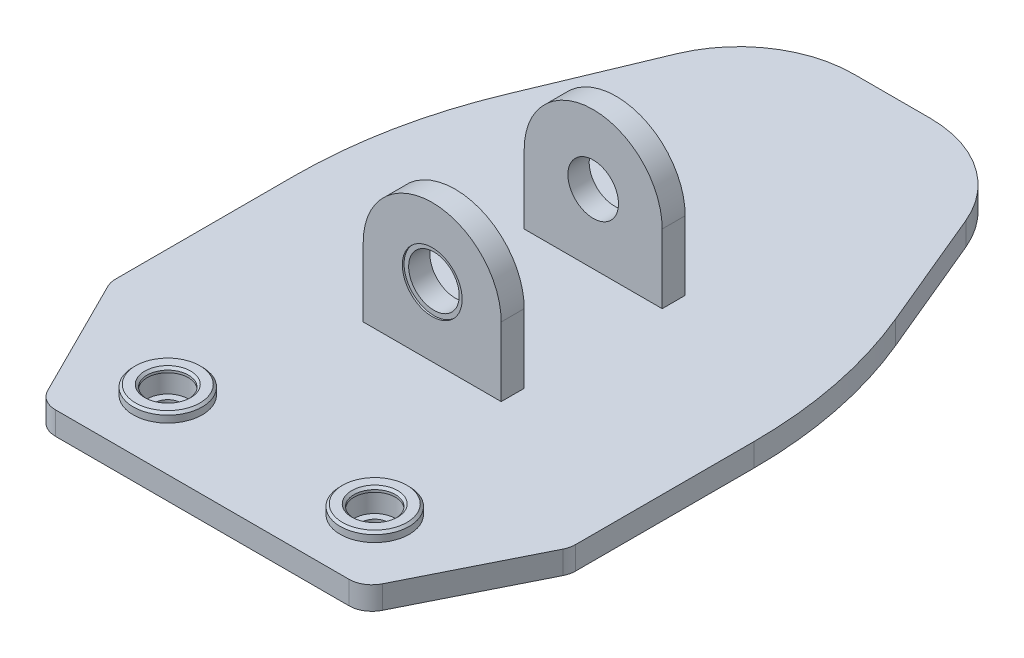
SolidWorks part; units mm, degrees
ref_plane "前视基准面" through (0, 0, 0) normal (0, 0, 1) x (1, 0, 0)
ref_plane "上视基准面" through (0, 0, 0) normal (0, 1, 0) x (1, 0, 0)
ref_plane "右视基准面" through (0, 0, 0) normal (1, 0, 0) x (0, 0, -1)
other "Configuration Table"
sketch "草图1" plane through (0, 0, 0) normal (0, 1, 0) x (1, 0, 0)
  line L0 (0, 0) -> (0, 255.8207) construction
  line L1 (-100, 0) -> (100, 0)
  line L2 (100, 0) -> (100, 180)
  line L3 (100, 180) -> (50, 300)
  line L4 (50, 300) -> (-50, 300)
  line L5 (-100, 180) -> (-50, 300)
  line L6 (-100, 0) -> (-100, 180)
  point P8 (0, 300)
  dimension "D1" = 300
  dimension "D2" = 100
  dimension "D3" = 120
  dimension "D4" = 50
extrude "凸台-拉伸1" add sketch "草图1" along normal blind 10
sketch "草图2" plane through (100, 0, 0) normal (1, 0, 0) x (0, 0, -1)
  line L0 (40, 100) -> (40, -10.3339) construction
  line L1 (0, 10) -> (0, 0) construction
  line L2 (0, 10) -> (0, 60)
  line L3 (80, 10) -> (80, 60)
  arc A0 (80, 60) -> (0, 60) centre (40, 60) ccw
  circle A1 centre (40, 60) radius 10
  line M6 (180, 10) -> (0, 10)
  dimension "D3" = 20
  dimension "D1" = 40
  dimension "D2" = 50
extrude "凸台-拉伸2" [suppressed] add sketch "草图2" against normal up to surface (200 mm away) contours A0 L0 A1 L3 M6 | L0 A0 L2 A1 M6 up to face at (-100, 5, -90)
sketch "草图3" [suppressed] plane through (0, 10, 0) normal (0, 1, 0) x (1, 0, 0)
  line L0 (0, 0) -> (0, 135.8056) construction
  line L1 (-100, 0) -> (100, 0) construction
  line L2 (-70, 0) -> (70, 0)
  line L3 (-70, 0) -> (-70, 100)
  line L4 (-70, 100) -> (70, 100)
  line L5 (70, 0) -> (70, 100)
  line L6 (100, 0) -> (100, 80) construction
  line L7 (-100, 80) -> (-100, 0) construction
  dimension "D1" = 30
  dimension "D2" = 30
  dimension "D3" = 100
extrude "切除-拉伸1" [suppressed] cut sketch "草图3" along normal blind 171
sketch "草图4" plane through (0, 0, 0) normal (0, 0, 1) x (1, 0, 0)
  line L0 (0, 0) -> (0, 92.3322) construction
  line L1 (30, 40) -> (30, 10)
  line L2 (-30, 40) -> (-30, 10)
  line L3 (-100, 10) -> (100, 10) construction
  arc A0 (-30, 40) -> (30, 40) centre (0, 40) cw
  circle A1 centre (0, 40) radius 11
  line M10 (100, 10) -> (-100, 10)
  dimension "D2" = 30
  dimension "D3" = 22
  dimension "D1" = 30
extrude "凸台-拉伸3" add sketch "草图4" against normal blind 80 from offset 100 contours L0 L1 A0 A1 M10 | L0 A1 A0 L2 M10 region at (-15.2547, 36.8238, 0) region at (15.2547, 36.8238, 0) offset against normal yes
sketch "草图5" plane through (0, 10, 0) normal (0, 1, 0) x (1, 0, 0)
  line L0 (-47.074, 140) -> (51.1394, 140) construction
  line L1 (30, 180) -> (-30, 180) construction
  line L2 (30, 100) -> (-30, 100) construction
  line L3 (-30, 100) -> (30, 100) construction
  line L4 (-40, 170) -> (40, 170)
  line L5 (-40, 170) -> (-40, 110)
  line L6 (-40, 110) -> (40, 110)
  line L7 (40, 170) -> (40, 110)
  line L8 (30, 180) -> (30, 100) construction
  line L9 (-30, 180) -> (-30, 100) construction
  dimension "D1" = 10
  dimension "D2" = 10
  dimension "D3" = 10
  dimension "D4" = 10
extrude "切除-拉伸2" cut sketch "草图5" along normal blind 110 contours L7 L6 L5 L4
fillet "圆角1" radius 50 2 edges at (-50, 5, -300) (50, 5, -300)
fillet "圆角2" radius 200 2 edges at (-100, 5, -180) (100, 5, -180)
sketch "草图6" [suppressed] plane through (100, 0, 0) normal (1, 0, 0) x (0, 0, -1)
  line L0 (40, 60) -> (40, -52.2503) construction
  circle A0 centre (40, 60) radius 10 construction
  circle A1 centre (40, 60) radius 10 construction
  arc A2 (73.0468, 82.5368) -> (6.9532, 82.5368) centre (40, -25) ccw
  arc A3 (80, 60) -> (0, 60) centre (40, 60) ccw construction
  arc A4 (73.0468, 82.5368) -> (6.9532, 82.5368) centre (40, 60) ccw
  dimension "D2" = 225
  dimension "D1" = 25
extrude "切除-拉伸3" [suppressed] cut sketch "草图6" against normal through all both and the other way through all contours A2 A4
sketch "草图7" plane through (0, 10, 0) normal (0, 1, 0) x (1, 0, 0)
  line L0 (0, 0) -> (0, 141.3983) construction
  line L1 (-100, 0) -> (100, 0) construction
  circle A0 centre (45, 30) radius 9
  dimension "D1" = 18
  dimension "D2" = 45
  dimension "D3" = 30
extrude "切除-拉伸6" cut sketch "草图7" against normal offset from surface (6 mm away) 4 contours A0 up to face at (0, 0, -186.7805)
sketch "草图10" plane through (0, 4, 0) normal (0, 1, 0) x (1, 0, 0)
  circle A0 centre (45, 30) radius 6
  dimension "D1" = 12
extrude "切除-拉伸7" cut sketch "草图10" against normal blind 28 contours A0
sketch "草图11" plane through (0, 10, 0) normal (0, 1, 0) x (1, 0, 0)
  circle A0 centre (45, 30) radius 12.5
  circle A1 centre (45, 30) radius 16.5
  dimension "D1" = 25
  dimension "D2" = 33
extrude "切除-拉伸8" [suppressed] cut sketch "草图11" against normal blind 5
sketch "草图12" plane through (0, 10, 0) normal (0, 1, 0) x (1, 0, 0)
  circle A0 centre (45, 30) radius 15
  dimension "D1" = 30
extrude "凸台-拉伸5" add sketch "草图12" along normal blind 4 contours A0
sketch "草图13" plane through (0, 14, 0) normal (0, 1, 0) x (1, 0, 0)
  circle A0 centre (45, 30) radius 9
  dimension "D1" = 18
extrude "切除-拉伸9" cut sketch "草图13" against normal blind 4
sketch "草图14" plane through (0, 14, 0) normal (0, 1, 0) x (1, 0, 0)
  circle A0 centre (45, 30) radius 9.75
  circle A2 centre (45, 30) radius 9 construction
  circle A3 centre (45, 30) radius 9
  circle M1 centre (45, 30) radius 9
  dimension "D1" = 19.5
extrude "卡簧槽" cut sketch "草图14" against normal blind 10 from offset 2 contours M1 | A0 region at (45, 14, -30) offset against normal yes
chamfer "倒角1" distance 1 angle 45 2 edges at (45, 14, -15) (45, 14, -21)
ref_plane "基准面1" through (0, 0, 0) normal (-1, 0, 0) x (0, 0, 1)
mirror "镜向1" about plane through (0, 0, 0) normal (-1, 0, 0) of "切除-拉伸6", "切除-拉伸7", "凸台-拉伸5", "切除-拉伸9", "卡簧槽", "倒角1"
sketch "草图16" plane through (0, 0, -100) normal (0, 0, 1) x (1, 0, 0)
  circle A0 centre (0, 40) radius 13
  dimension "D1" = 26
extrude "切除-拉伸10" cut sketch "草图16" against normal blind 0.75
sketch "草图17" plane through (0, 0, -180) normal (0, 0, -1) x (-1, 0, 0)
  circle A0 centre (0, 40) radius 13
  dimension "D1" = 26
extrude "切除-拉伸11" cut sketch "草图17" against normal blind 0.75 contours A0
sketch "草图18" plane through (-100, 0, 0) normal (-1, 0, 0) x (0, 0, 1)
  line L0 (-30, 92.2697) -> (-30, -20.0308) construction
  line L1 (-40, 10) -> (-40, 30)
  line L2 (-140, 10) -> (0, 10) construction
  line L3 (-20, 30) -> (-20, 10)
  line L4 (-40, 10) -> (-20, 10)
  arc A0 (-20, 30) -> (-40, 30) centre (-30, 30) ccw
  circle A1 centre (-30, 30) radius 2.5
  dimension "D2" = 5
  dimension "D4" = 10
  dimension "D1" = 30
  dimension "D3" = 20
extrude "凸台-拉伸6" [suppressed] add sketch "草图18" against normal up to surface (200 mm away) contours A1 L0 | L0 A1 | L3 L4 L1 A0 up to face at (100, 5, -70)
sketch "草图20" plane through (0, 10, 0) normal (0, 1, 0) x (1, 0, 0)
  line L0 (0, 0) -> (0, 309.5578) construction
  line L1 (-100, 0) -> (100, 0) construction
  line L2 (-60.0864, 49.2403) -> (-60.0864, 11.6041)
  line L3 (75.0864, 51.8093) -> (107.8414, 51.8093)
  line L4 (75.0864, 51.8093) -> (75.0864, 7.1083)
  line L5 (75.0864, 7.1083) -> (107.8414, 7.1083)
  line L6 (107.8414, 51.8093) -> (107.8414, 7.1083)
  line L7 (15, 49.2403) -> (60.0864, 49.2403)
  line L8 (15, 49.2403) -> (15, 11.6041)
  line L9 (15, 11.6041) -> (60.0864, 11.6041)
  line L10 (60.0864, 49.2403) -> (60.0864, 11.6041)
  line L11 (-15, 11.6041) -> (-60.0864, 11.6041)
  line L12 (-15, 49.2403) -> (-15, 11.6041)
  line L13 (-15, 49.2403) -> (-60.0864, 49.2403)
  line L14 (-107.8414, 51.8093) -> (-107.8414, 7.1083)
  line L15 (-75.0864, 7.1083) -> (-107.8414, 7.1083)
  line L16 (-75.0864, 51.8093) -> (-75.0864, 7.1083)
  line L17 (-75.0864, 51.8093) -> (-107.8414, 51.8093)
  dimension "D1" = 15
  dimension "D2" = 15
extrude "切除-拉伸12" [suppressed] cut sketch "草图20" along normal through all
chamfer "倒角2" distance 30 distance2 60 1 edges at (100, 5, 0) first distance on face at (0, 5, 0)
chamfer "倒角3" distance 60 distance2 30 1 edges at (-100, 5, 0) first distance on face at (-100, 5, -70)
fillet "圆角3" radius 10 4 edges at (-70, 5, 0) (-100, 5, -60) (70, 5, 0) (100, 5, -60)
ref_plane "脚底板中心面" through (0, 0, 0) normal (-1, 0, 0) x (0, 0, 1)
ref_plane "基准面3" through (0, 0, -30) normal (0, 0, 1) x (1, 0, 0)
sketch "草图22" plane through (0, 0, -30) normal (0, 0, 1) x (1, 0, 0)
  line L0 (45, 18.5577) -> (45, -23.1228) construction
  line L1 (-45, 24.8334) -> (-45, -23.1228) construction
  line L2 (45, 0) -> (45, 4) construction
  line L3 (-45, 0) -> (-45, 4) construction
ref_plane "基准面4" through (-45, 0, 0) normal (-1, 0, 0) x (0, 0, 1)
